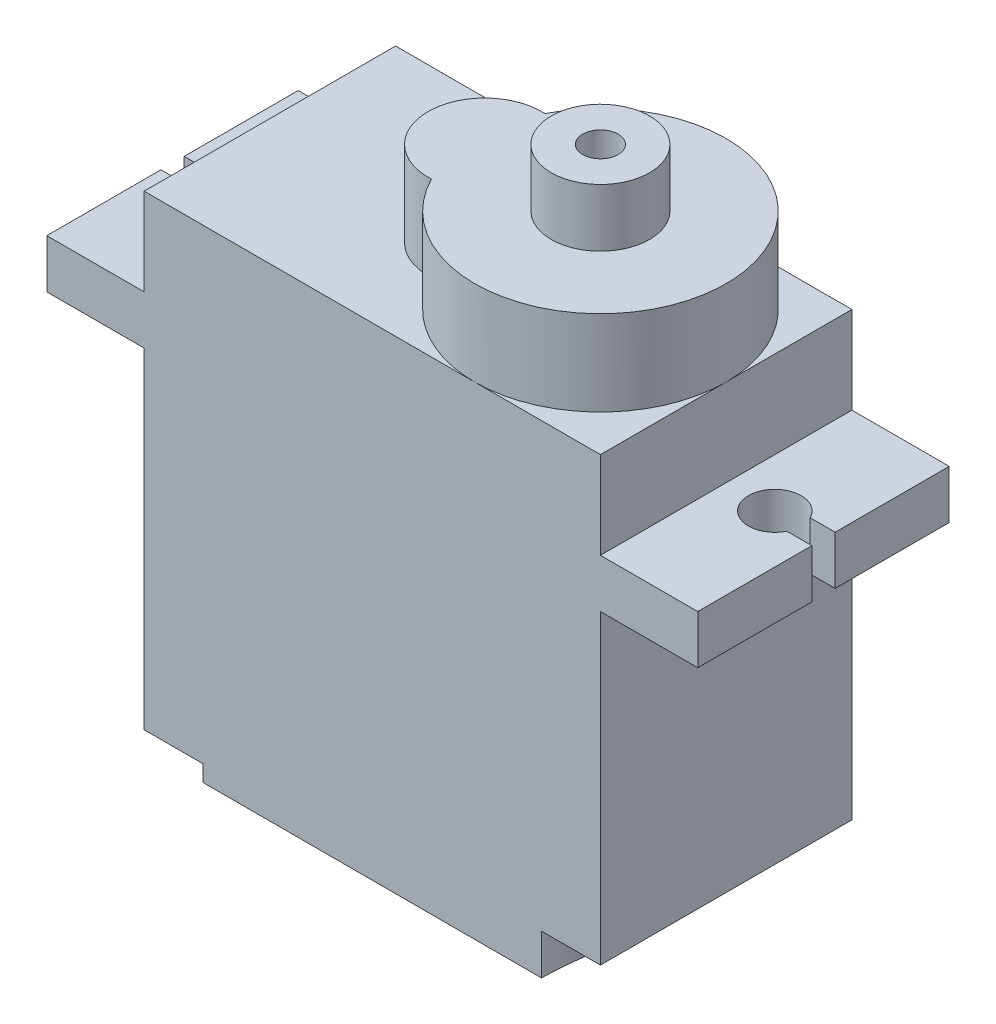
SolidWorks part; units mm, degrees
ref_plane "Alzado" through (0, 0, 0) normal (0, 0, 1) x (1, 0, 0)
ref_plane "Planta" through (0, 0, 0) normal (0, 1, 0) x (1, 0, 0)
ref_plane "Vista lateral" through (0, 0, 0) normal (1, 0, 0) x (0, 0, -1)
sketch "Croquis1" plane through (0, 0, 0) normal (0, 0, 1) x (1, 0, 0)
  line L0 (0, 11.9) -> (0, -11.9) construction
  line L4 (-11.25, -11.9) -> (-11.25, 11.9)
  line L5 (-11.25, 11.9) -> (11.25, 11.9)
  line L6 (-11.25, -11.9) -> (11.25, -11.9)
  line L7 (-16.05, 5.2) -> (-11.25, 5.2)
  line L8 (-16.05, 5.2) -> (-16.05, 7.6)
  line L9 (-16.05, 7.6) -> (-11.25, 7.6)
  line L10 (-11.25, 5.2) -> (-11.25, 7.6)
  line L11 (-16.05, 5.2) -> (-11.25, 7.6) construction
  line L12 (-16.05, 7.6) -> (-11.25, 5.2) construction
  line L14 (11.25, -11.9) -> (11.25, 11.9)
  line L16 (16.05, 7.6) -> (11.25, 7.6)
  line L17 (11.25, 5.2) -> (11.25, 7.6)
  line L18 (16.05, 5.2) -> (11.25, 5.2)
  line L19 (16.05, 5.2) -> (16.05, 7.6)
  point P0 (0, 0)
  point P2 (-11.25, 0)
  point P6 (-13.65, 6.4)
  dimension "D1" = 23.8
  dimension "D2" = 2.4
  dimension "D3" = 22.5
  dimension "D4" = 4.8
  dimension "D5" = 4.3
extrude "Saliente-Extruir1" add sketch "Croquis1" along normal mid plane 12.4 contours L9 L8 L7 L4 | L6 L14 L5 L4 | L18 L19 L16 L14 region at (0, 0, 0) region at (-13.65, 6.4, 0) region at (13.65, 6.4, 0)
sketch "Croquis2" plane through (0, 11.9, 0) normal (0, 1, 0) x (1, 0, 0)
  line L0 (-11.25, 6.2) -> (11.25, 6.2) construction
  line L1 (-11.25, -6.2) -> (11.25, -6.2) construction
  line L2 (11.25, -6.2) -> (11.25, 6.2) construction
  line L3 (-0.65, 0) -> (-3.45, 0) construction
  arc A0 (-0.4842, -2.7951) -> (-0.4842, 2.7951) centre (5.05, 0) ccw
  arc A1 (-0.4842, 2.7951) -> (-0.4842, -2.7951) centre (-0.65, 0) ccw
  dimension "D2" = 5.6
  dimension "D1" = 14.7
extrude "Saliente-Extruir2" add sketch "Croquis2" along normal blind 4.2
sketch "Croquis3" plane through (0, 7.6, 0) normal (0, 1, 0) x (1, 0, 0)
  line L0 (0, -6.2) -> (0, 6.2) construction
  line L1 (-11.25, -6.2) -> (5.05, -6.2) construction
  line L2 (-11.25, 6.2) -> (5.05, 6.2) construction
  line L3 (16.05, 0.575) -> (14.8159, 0.575)
  line L4 (16.05, -6.2) -> (16.05, 6.2) construction
  line L5 (16.05, -0.575) -> (14.8159, -0.575)
  line L6 (16.05, 0.575) -> (16.05, -0.575)
  line L7 (-16.05, 0.575) -> (-14.8159, 0.575)
  line L8 (-16.05, 0.575) -> (-16.05, -0.575)
  line L9 (-16.05, -0.575) -> (-14.8159, -0.575)
  arc A1 (14.8159, 0.575) -> (14.8159, -0.575) centre (13.65, 0) ccw
  arc A2 (-14.8159, 0.575) -> (-14.8159, -0.575) centre (-13.65, 0) cw
  point P16 (16.05, 0)
  point P18 (16.05, 0)
  dimension "D2" = 2.6
  dimension "D1" = 1.15
  dimension "D3" = 2.4
extrude "Cortar-Extruir1" cut sketch "Croquis3" against normal up to next
sketch "Croquis4" plane through (0, -11.9, 0) normal (0, -1, 0) x (1, 0, 0)
  line L0 (0, 6.2) -> (0, -6.2) construction
  line L1 (-11.25, 0) -> (11.25, 0) construction
  line L2 (-11.25, 3.3) -> (-11.25, 6.2)
  line L3 (-11.25, 6.2) -> (-8.35, 6.2)
  line L4 (-11.25, -6.2) -> (11.25, -6.2)
  line L5 (11.25, -6.2) -> (11.25, 6.2)
  line L6 (11.25, 6.2) -> (-11.25, 6.2)
  line L7 (-11.25, 6.2) -> (-11.25, -6.2)
  line L8 (-11.25, -6.2) -> (11.25, -6.2)
  line L9 (11.25, -6.2) -> (11.25, 6.2)
  line L10 (11.25, 6.2) -> (-11.25, 6.2)
  line L11 (-11.25, 6.2) -> (-11.25, -6.2)
  line L12 (-11.25, -3.3) -> (-11.25, -6.2)
  line L13 (-11.25, -6.2) -> (-8.35, -6.2)
  line L14 (11.25, 3.3) -> (11.25, 6.2)
  line L15 (11.25, 6.2) -> (8.35, 6.2)
  line L16 (11.25, -3.3) -> (11.25, -6.2)
  line L17 (11.25, -6.2) -> (8.35, -6.2)
  line L18 (8.35, 6.2) -> (8.35, -6.2)
  line L19 (9.75, -1.875) -> (11.25, -1.875)
  line L20 (9.75, -1.875) -> (9.75, 1.875)
  line L21 (9.75, 1.875) -> (11.25, 1.875)
  line L22 (11.25, -1.875) -> (11.25, 1.875)
  line L23 (9.75, -1.875) -> (11.25, 1.875) construction
  line L24 (9.75, 1.875) -> (11.25, -1.875) construction
  arc A0 (-8.35, 6.2) -> (-11.25, 3.3) centre (-11.25, 6.2) cw
  arc A1 (-8.35, -6.2) -> (-11.25, -3.3) centre (-11.25, -6.2) ccw
  arc A2 (8.35, 6.2) -> (11.25, 3.3) centre (11.25, 6.2) ccw
  arc A3 (8.35, -6.2) -> (11.25, -3.3) centre (11.25, -6.2) cw
  point P17 (10.5, 0)
  dimension "D2" = 2.9
  dimension "D3" = 3.75
  dimension "D4" = 1.5
  dimension "D1" = 0
extrude "Cortar-Extruir3" cut sketch "Croquis4" against normal blind 0.8 contours A0 L16 L4 | L17 A1 L11 region at (-10.0192, -11.9, 4.9692) region at (-10.0192, -11.9, -4.9692)
extrude "Cortar-Extruir4" cut sketch "Croquis4<5>" against normal blind 2 contours L16 A2 L9 | L21 L20 L19 A3 | A3 L17 region at (10.0192, -11.9, 4.9692) region at (10.0192, -11.9, -4.9692) region at (10.5, -11.9, 0)
sketch "Croquis4<5>" plane through (0, -11.9, 0) normal (0, -1, 0) x (1, 0, 0) same geometry as "Croquis4"
sketch "Croquis6" plane through (0, 0, -6.2) normal (0, 0, -1) x (-1, 0, 0)
  line L0 (-11.25, -9.9) -> (-8.35, -11.9)
  line L1 (-8.35, -11.9) -> (-11.25, -11.9)
  line L2 (-11.25, -11.9) -> (-11.25, -9.9)
extrude "Cortar-Extruir5" cut sketch "Croquis6" against normal through all
sketch "Croquis7" plane through (0, 16.1, 0) normal (0, 1, 0) x (1, 0, 0)
  circle A0 centre (5.05, 0) radius 2.425
  circle A1 centre (5.05, 0) radius 0.875
  dimension "D1" = 4.85
  dimension "D2" = 1.55
extrude "Saliente-Extruir4" add sketch "Croquis7" along normal blind 2.85
